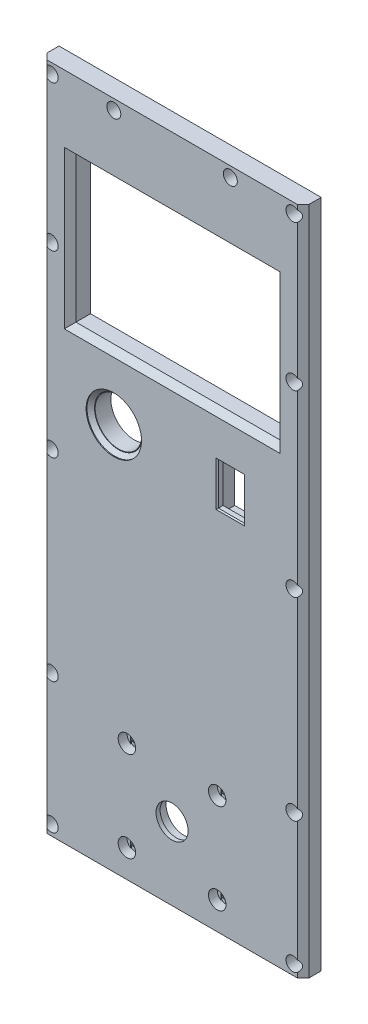
SolidWorks part; units mm, degrees
ref_plane "Front Plane" through (0, 0, 0) normal (0, 0, 1) x (1, 0, 0)
ref_plane "Top Plane" through (0, 0, 0) normal (0, 1, 0) x (1, 0, 0)
ref_plane "Right Plane" through (0, 0, 0) normal (1, 0, 0) x (0, 0, -1)
sketch "Sketch1" plane through (0, 0, 0) normal (0, 0, 1) x (1, 0, 0)
  line L1 (-45, -115) -> (45, -115)
  line L2 (-45, -115) -> (-45, 115)
  line L3 (-45, 115) -> (45, 115)
  line L4 (45, -115) -> (45, 115)
  line L5 (-45, -115) -> (45, 115) construction
  line L6 (-45, 115) -> (45, -115) construction
  line L7 (-38, -108) -> (38, -108)
  line L8 (-38, -108) -> (-38, 108)
  line L9 (-38, 108) -> (38, 108)
  line L10 (38, -108) -> (38, 108)
  line L11 (-38, -108) -> (38, 108) construction
  line L12 (-38, 108) -> (38, -108) construction
  point P0 (0, 0)
  point P6 (0, 0)
  dimension "D1" = 230
  dimension "D2" = 90
  dimension "D3" = 7
  dimension "D4" = 7
extrude "Boss-Extrude1" add sketch "Sketch1" along normal blind 7
sketch "Sketch2" plane through (0, 0, 7) normal (0, 0, 1) x (1, 0, 0)
  line L0 (38, -108) -> (38, 108) construction
  line L1 (-38, -108) -> (38, -108)
  line L2 (-38, -108) -> (-38, -58)
  line L3 (-38, -58) -> (38, -58)
  line L4 (38, -108) -> (38, -58)
  dimension "D1" = 50
extrude "Boss-Extrude2" add sketch "Sketch2" against normal up to surface (7 mm away) up to face at (0, 0, 0)
sketch "Sketch3" plane through (0, 0, 0) normal (0, 0, -1) x (-1, 0, 0)
  line L0 (0, -115) -> (0, -90) construction
  line L1 (45, -115) -> (-45, -115) construction
  circle A0 centre (0, -90) radius 5.5
  dimension "D1" = 11
  dimension "D2" = 25
extrude "Cut-Extrude1" cut sketch "Sketch3" against normal through all
sketch "Sketch4" plane through (0, 0, 0) normal (0, 0, -1) x (-1, 0, 0)
  circle A0 centre (0, -90) radius 6.05
  dimension "D1" = 12.1
extrude "Cut-Extrude2" cut sketch "Sketch4" against normal offset from surface (5.6 mm away) 1.4 up to face at (-5.5, -90, 7)
sketch "Sketch5" plane through (0, 0, 0) normal (0, 0, -1) x (-1, 0, 0)
  circle A0 centre (0, -90) radius 12
  dimension "D1" = 24
extrude "Cut-Extrude3" cut sketch "Sketch5" against normal offset from surface (3 mm away) 2.6 up to face at (-6.05, -90, 5.6)
sketch "Sketch6" plane through (0, 0, 0) normal (0, 0, -1) x (-1, 0, 0)
  line L1 (-15.5, -105.5) -> (15.5, -105.5) construction
  line L2 (-15.5, -105.5) -> (-15.5, -74.5) construction
  line L3 (-15.5, -74.5) -> (15.5, -74.5) construction
  line L4 (15.5, -105.5) -> (15.5, -74.5) construction
  line L5 (-15.5, -105.5) -> (15.5, -74.5) construction
  line L6 (-15.5, -74.5) -> (15.5, -105.5) construction
  circle A0 centre (-15.5, -74.5) radius 1.7
  circle A1 centre (15.5, -74.5) radius 1.7
  circle A2 centre (15.5, -105.5) radius 1.7
  circle A3 centre (-15.5, -105.5) radius 1.7
  point P0 (0, -90)
  dimension "D2" = 3.4
  dimension "D1" = 31
extrude "Cut-Extrude4" cut sketch "Sketch6" against normal through all
sketch "Sketch7" plane through (0, 0, 0) normal (0, 0, -1) x (-1, 0, 0)
  line L1 (-30, -112.5) -> (30, -112.5)
  line L2 (-30, -112.5) -> (-30, -67.5)
  line L3 (-30, -67.5) -> (30, -67.5)
  line L4 (30, -112.5) -> (30, -67.5)
  line L5 (-30, -112.5) -> (30, -67.5) construction
  line L6 (-30, -67.5) -> (30, -112.5) construction
  point P0 (0, -90)
  dimension "D1" = 60
  dimension "D2" = 45
extrude "Cut-Extrude5" cut sketch "Sketch7" against normal blind 1
sketch "Sketch8" plane through (0, 0, 7) normal (0, 0, 1) x (1, 0, 0)
  circle A0 centre (-15.5, -74.5) radius 3
  circle A1 centre (15.5, -74.5) radius 3
  circle A2 centre (15.5, -105.5) radius 3
  circle A3 centre (-15.5, -105.5) radius 3
  dimension "D1" = 6
extrude "Cut-Extrude6" cut sketch "Sketch8" against normal blind 3
sketch "Sketch9" plane through (0, 0, 7) normal (0, 0, 1) x (1, 0, 0)
  line L0 (-45, 115) -> (-45, -115) construction
  line L1 (-41.5, -111.5) -> (41.5, -111.5) construction
  line L2 (-41.5, -111.5) -> (-41.5, 111.5) construction
  line L3 (-41.5, 111.5) -> (41.5, 111.5) construction
  line L4 (41.5, -111.5) -> (41.5, 111.5) construction
  line L5 (-41.5, -111.5) -> (41.5, 111.5) construction
  line L6 (-41.5, 111.5) -> (41.5, -111.5) construction
  line L7 (45, 115) -> (-45, 115) construction
  circle A0 centre (-41.5, 111.5) radius 1.45
  circle A1 centre (41.5, 111.5) radius 1.45
  circle A4 centre (-41.5, -111.5) radius 1.45
  circle A5 centre (41.5, -111.5) radius 1.45
  circle A6 centre (-41.5, 61.5) radius 1.45
  circle A7 centre (41.5, 61.5) radius 1.45
  circle A8 centre (41.5, -66.5) radius 1.45
  circle A9 centre (-41.5, -66.5) radius 1.45
  circle A10 centre (-41.5, 0) radius 1.45
  circle A11 centre (41.5, 0) radius 1.45
  point P0 (0, 0)
  dimension "D3" = 2.9
  dimension "D1" = 3.5
  dimension "D2" = 3.5
  dimension "D4" = 45
  dimension "D5" = 50
extrude "Cut-Extrude7" cut sketch "Sketch9" against normal through all
sketch "Sketch10" plane through (0, 0, 7) normal (0, 0, 1) x (1, 0, 0)
  circle A0 centre (-41.5, 111.5) radius 2.4
  circle A1 centre (41.5, 61.5) radius 2.4
  circle A2 centre (-41.5, 61.5) radius 2.4
  circle A3 centre (41.5, 111.5) radius 2.4
  circle A4 centre (-41.5, -111.5) radius 2.4
  circle A5 centre (41.5, -111.5) radius 2.4
  circle A6 centre (-41.5, -66.5) radius 2.4
  circle A7 centre (41.5, -66.5) radius 2.4
  circle A8 centre (-41.5, 0) radius 2.4
  circle A9 centre (41.5, 0) radius 2.4
  dimension "D1" = 4.8
extrude "Cut-Extrude8" cut sketch "Sketch10" against normal blind 5
chamfer "Chamfer1" distance 2 angle 45 2 edges at (-45, 0, 7) (45, 0, 7)
sketch "Sketch11" plane through (0, 0, 7) normal (0, 0, 1) x (1, 0, 0)
  line L0 (38, -58) -> (38, 108) construction
  line L1 (-38, -58) -> (38, -58)
  line L2 (-38, -58) -> (-38, -36.4)
  line L3 (-38, -36.4) -> (38, -36.4)
  line L4 (38, -58) -> (38, -36.4)
  line L5 (-43, -115) -> (43, -115) construction
  dimension "D1" = 78.6
extrude "Boss-Extrude3" add sketch "Sketch11" against normal up to surface (7 mm away) up to face at (-40.05, 0, 0)
sketch "Sketch12" plane through (0, 0, 7) normal (0, 0, 1) x (1, 0, 0)
  line L0 (-41.5, 111.5) -> (41.5, 111.5) construction
  line L1 (-20, 111.5) -> (20, 111.5) construction
  circle A0 centre (-20, 111.5) radius 1.45
  circle A1 centre (20, 111.5) radius 1.45
  circle A2 centre (-41.5, 111.5) radius 1.45 construction
  point P7 (0, 111.5)
  dimension "D1" = 40
extrude "Cut-Extrude9" cut sketch "Sketch12" against normal through all
sketch "Sketch13" plane through (0, 0, 7) normal (0, 0, 1) x (1, 0, 0)
  circle A0 centre (-20, 111.5) radius 2.4
  circle A1 centre (20, 111.5) radius 2.4
  circle A2 centre (-41.5, 111.5) radius 2.4 construction
extrude "Cut-Extrude10" cut sketch "Sketch13" against normal up to surface (5 mm away) up to face at (-39.1, 111.5, 2)
chamfer "Chamfer2" distance 0.8 angle 45 12 edges at (0, -115, 0) (-45, 0, 0) (0, 115, 0) (45, 0, 0) (38, 35.8, 7) (0, 108, 7) (-38, 35.8, 7) (0, -36.4, 7) (-38, 35.8, 0) (0, 108, 0) (38, 35.8, 0) (0, -36.4, 0)
sketch "Sketch14" plane through (0, 0, 2) normal (0, 0, 1) x (1, 0, 0)
  line L2 (-42.95, -68.4125) -> (-42.95, -64.5875)
  line L4 (-40.05, -68.4125) -> (-40.05, -64.5875)
  line L5 (-42.95, -68.4125) -> (-40.05, -64.5875) construction
  line L6 (-42.95, -64.5875) -> (-40.05, -68.4125) construction
  line L14 (-42.95, -113.4125) -> (-42.95, -109.5875)
  line L16 (-40.05, -113.4125) -> (-40.05, -109.5875)
  line L17 (-42.95, -113.4125) -> (-40.05, -109.5875) construction
  line L18 (-42.95, -109.5875) -> (-40.05, -113.4125) construction
  line L26 (-42.95, 59.5875) -> (-42.95, 63.4125)
  line L28 (-40.05, 59.5875) -> (-40.05, 63.4125)
  line L29 (-42.95, 59.5875) -> (-40.05, 63.4125) construction
  line L30 (-42.95, 63.4125) -> (-40.05, 59.5875) construction
  line L32 (-21.45, 109.5875) -> (-21.45, 113.4125)
  line L34 (-18.55, 109.5875) -> (-18.55, 113.4125)
  line L35 (-21.45, 109.5875) -> (-18.55, 113.4125) construction
  line L36 (-21.45, 113.4125) -> (-18.55, 109.5875) construction
  line L38 (-42.95, 109.5875) -> (-42.95, 113.4125)
  line L40 (-40.05, 109.5875) -> (-40.05, 113.4125)
  line L41 (-42.95, 109.5875) -> (-40.05, 113.4125) construction
  line L42 (-42.95, 113.4125) -> (-40.05, 109.5875) construction
  arc A0 (-43, -68.3735) -> (-43, -64.6265) centre (-41.5, -66.5) ccw construction
  circle A2 centre (-41.5, -111.5) radius 2.4 construction
  circle A4 centre (-41.5, 61.5) radius 2.4 construction
  circle A5 centre (-20, 111.5) radius 2.4 construction
  circle A6 centre (-41.5, 111.5) radius 2.4 construction
  circle A7 centre (-41.5, 111.5) radius 1.45 construction
  circle A8 centre (-20, 111.5) radius 1.45 construction
  circle A9 centre (-41.5, 61.5) radius 1.45 construction
  circle A10 centre (-41.5, -66.5) radius 1.45 construction
  circle A12 centre (-41.5, -111.5) radius 1.45 construction
  arc A16 (-21.45, 109.5875) -> (-18.55, 109.5875) centre (-20, 111.5) ccw
  arc A17 (-40.05, 113.4125) -> (-42.95, 113.4125) centre (-41.5, 111.5) ccw
  arc A18 (-40.05, 63.4125) -> (-42.95, 63.4125) centre (-41.5, 61.5) ccw
  arc A20 (-42.95, -68.4125) -> (-40.05, -68.4125) centre (-41.5, -66.5) ccw
  arc A22 (-40.05, -109.5875) -> (-42.95, -109.5875) centre (-41.5, -111.5) ccw
  arc A23 (-42.95, 109.5875) -> (-40.05, 109.5875) centre (-41.5, 111.5) ccw
  arc A24 (-18.55, 113.4125) -> (-21.45, 113.4125) centre (-20, 111.5) ccw
  arc A25 (-42.95, 59.5875) -> (-40.05, 59.5875) centre (-41.5, 61.5) ccw
  arc A26 (-40.05, -64.5875) -> (-42.95, -64.5875) centre (-41.5, -66.5) ccw
  arc A29 (-42.95, -113.4125) -> (-40.05, -113.4125) centre (-41.5, -111.5) ccw
  point P0 (-41.5, -66.5)
  point P17 (-41.5, -111.5)
  point P33 (-41.5, 61.5)
  point P41 (-20, 111.5)
  point P49 (-41.5, 111.5)
extrude "Cut-Extrude11" cut sketch "Sketch14" against normal blind 0.2
sketch "Sketch15" plane through (0, 0, 1.8) normal (0, 0, 1) x (1, 0, 0)
  line L0 (-40.05, -111.5) -> (-40.05, -109.5875) construction
  line L1 (-42.95, -112.95) -> (-40.05, -112.95)
  line L2 (-42.95, -112.95) -> (-42.95, -110.05)
  line L3 (-42.95, -110.05) -> (-40.05, -110.05)
  line L4 (-40.05, -112.95) -> (-40.05, -110.05)
  line L5 (-42.95, -112.95) -> (-40.05, -110.05) construction
  line L6 (-42.95, -110.05) -> (-40.05, -112.95) construction
  line L7 (-40.05, 61.5) -> (-40.05, 63.4125) construction
  line L8 (-42.95, -67.95) -> (-40.05, -67.95)
  line L9 (-42.95, -67.95) -> (-42.95, -65.05)
  line L10 (-42.95, -65.05) -> (-40.05, -65.05)
  line L11 (-40.05, -67.95) -> (-40.05, -65.05)
  line L12 (-42.95, -67.95) -> (-40.05, -65.05) construction
  line L13 (-42.95, -65.05) -> (-40.05, -67.95) construction
  line L14 (-42.95, 60.05) -> (-40.05, 60.05)
  line L15 (-42.95, 60.05) -> (-42.95, 62.95)
  line L16 (-42.95, 62.95) -> (-40.05, 62.95)
  line L17 (-40.05, 60.05) -> (-40.05, 62.95)
  line L18 (-42.95, 60.05) -> (-40.05, 62.95) construction
  line L19 (-42.95, 62.95) -> (-40.05, 60.05) construction
  line L20 (-40.05, 109.5875) -> (-40.05, 113.4125) construction
  line L21 (-42.95, 110.05) -> (-40.05, 110.05)
  line L22 (-42.95, 110.05) -> (-42.95, 112.95)
  line L23 (-42.95, 112.95) -> (-40.05, 112.95)
  line L24 (-40.05, 110.05) -> (-40.05, 112.95)
  line L25 (-42.95, 110.05) -> (-40.05, 112.95) construction
  line L26 (-42.95, 112.95) -> (-40.05, 110.05) construction
  line L27 (-18.55, 109.5875) -> (-18.55, 113.4125) construction
  line L28 (-21.45, 110.05) -> (-18.55, 110.05)
  line L29 (-21.45, 110.05) -> (-21.45, 112.95)
  line L30 (-21.45, 112.95) -> (-18.55, 112.95)
  line L31 (-18.55, 110.05) -> (-18.55, 112.95)
  line L32 (-21.45, 110.05) -> (-18.55, 112.95) construction
  line L33 (-21.45, 112.95) -> (-18.55, 110.05) construction
  arc A0 (-40.05, -66.5) -> (-42.95, -66.5) centre (-41.5, -66.5) ccw construction
  arc A1 (-40.05, 61.5) -> (-42.95, 61.5) centre (-41.5, 61.5) ccw construction
  arc A2 (-18.55, 111.5) -> (-21.45, 111.5) centre (-20, 111.5) ccw construction
  arc A3 (-40.05, 111.5) -> (-42.95, 111.5) centre (-41.5, 111.5) ccw construction
  point P0 (-41.5, -111.5)
  point P8 (-41.5, -66.5)
  point P17 (-41.5, 61.5)
  point P28 (-41.5, 111.5)
  point P36 (-20, 111.5)
extrude "Cut-Extrude12" cut sketch "Sketch15" against normal blind 0.2
sketch "Sketch16" plane through (0, 0, 4) normal (0, 0, 1) x (1, 0, 0)
  line L2 (-17.2, -76.9718) -> (-17.2, -72.0282)
  line L4 (-13.8, -76.9718) -> (-13.8, -72.0282)
  line L5 (-17.2, -76.9718) -> (-13.8, -72.0282) construction
  line L6 (-17.2, -72.0282) -> (-13.8, -76.9718) construction
  line L8 (-17.2, -107.9718) -> (-17.2, -103.0282)
  line L10 (-13.8, -107.9718) -> (-13.8, -103.0282)
  line L11 (-17.2, -107.9718) -> (-13.8, -103.0282) construction
  line L12 (-17.2, -103.0282) -> (-13.8, -107.9718) construction
  circle A0 centre (-15.5, -74.5) radius 3 construction
  circle A1 centre (-15.5, -105.5) radius 3 construction
  circle A2 centre (-15.5, -105.5) radius 1.7 construction
  circle A3 centre (-15.5, -74.5) radius 1.7 construction
  circle A4 centre (-15.5, -105.5) radius 3 construction
  circle A5 centre (-15.5, -74.5) radius 3 construction
  arc A6 (-13.8, -103.0282) -> (-17.2, -103.0282) centre (-15.5, -105.5) ccw
  arc A7 (-17.2, -76.9718) -> (-13.8, -76.9718) centre (-15.5, -74.5) ccw
  arc A8 (-13.8, -72.0282) -> (-17.2, -72.0282) centre (-15.5, -74.5) ccw
  arc A9 (-17.2, -107.9718) -> (-13.8, -107.9718) centre (-15.5, -105.5) ccw
  point P0 (-15.5, -74.5)
  point P8 (-15.5, -105.5)
extrude "Cut-Extrude13" cut sketch "Sketch16" against normal blind 0.2
sketch "Sketch17" plane through (0, 0, 3.8) normal (0, 0, 1) x (1, 0, 0)
  line L0 (-13.8, -76.9718) -> (-13.8, -72.0282) construction
  line L1 (-17.2, -76.2) -> (-13.8, -76.2)
  line L2 (-17.2, -76.2) -> (-17.2, -72.8)
  line L3 (-17.2, -72.8) -> (-13.8, -72.8)
  line L4 (-13.8, -76.2) -> (-13.8, -72.8)
  line L5 (-17.2, -76.2) -> (-13.8, -72.8) construction
  line L6 (-17.2, -72.8) -> (-13.8, -76.2) construction
  line L7 (-13.8, -107.9718) -> (-13.8, -103.0282) construction
  line L8 (-17.2, -107.2) -> (-13.8, -107.2)
  line L9 (-17.2, -107.2) -> (-17.2, -103.8)
  line L10 (-17.2, -103.8) -> (-13.8, -103.8)
  line L11 (-13.8, -107.2) -> (-13.8, -103.8)
  line L12 (-17.2, -107.2) -> (-13.8, -103.8) construction
  line L13 (-17.2, -103.8) -> (-13.8, -107.2) construction
  arc A0 (-13.8, -105.5) -> (-17.2, -105.5) centre (-15.5, -105.5) ccw construction
  arc A1 (-13.8, -74.5) -> (-17.2, -74.5) centre (-15.5, -74.5) ccw construction
  point P0 (-15.5, -74.5)
  point P8 (-15.5, -105.5)
extrude "Cut-Extrude14" cut sketch "Sketch17" against normal blind 0.2
mirror "Mirror1" about plane through (0, 0, 0) normal (1, 0, 0) of "Cut-Extrude12", "Cut-Extrude13", "Cut-Extrude14", "Cut-Extrude11"
sketch "Sketch18" plane through (0, 0, 7) normal (0, 0, 1) x (1, 0, 0)
  line L0 (38.8, 108.8) -> (38.8, -37.2) construction
  line L1 (-38.8, 108.8) -> (38.8, 108.8)
  line L2 (-38.8, 108.8) -> (-38.8, 70.8)
  line L3 (-38.8, 70.8) -> (38.8, 70.8)
  line L4 (38.8, 108.8) -> (38.8, 70.8)
  dimension "D1" = 38
extrude "Boss-Extrude4" add sketch "Sketch18" against normal up to surface (7 mm away) up to face at (0, 35.8, 0)
chamfer "Chamfer3" distance 0.8 angle 45 1 edges at (0, 70.8, 7)
sketch "Sketch19" plane through (0, 0, 7) normal (0, 0, 1) x (1, 0, 0)
  line L1 (-38.8, 71.6) -> (38.8, 71.6)
  line L2 (-38.8, 71.6) -> (-38.8, -37.2)
  line L3 (-38.8, -37.2) -> (38.8, -37.2)
  line L4 (38.8, 71.6) -> (38.8, -37.2)
extrude "Boss-Extrude5" add sketch "Sketch19" against normal up to surface (7 mm away) up to face at (0, 16.8, 0)
sketch "Sketch20" plane through (0, 0, 2) normal (0, 0, 1) x (1, 0, 0)
  line L2 (-42.95, -1.9125) -> (-42.95, 1.9125)
  line L4 (-40.05, -1.9125) -> (-40.05, 1.9125)
  line L5 (-42.95, -1.9125) -> (-40.05, 1.9125) construction
  line L6 (-42.95, 1.9125) -> (-40.05, -1.9125) construction
  arc A0 (-43, -1.8735) -> (-43, 1.8735) centre (-41.5, 0) ccw construction
  circle A1 centre (-41.5, 0) radius 1.45 construction
  arc A2 (-42.95, -1.9125) -> (-40.05, -1.9125) centre (-41.5, 0) ccw
  arc A3 (-40.05, 1.9125) -> (-42.95, 1.9125) centre (-41.5, 0) ccw
  point P0 (-41.5, 0)
extrude "Cut-Extrude15" cut sketch "Sketch20" against normal blind 0.2
sketch "Sketch21" plane through (0, 0, 1.8) normal (0, 0, 1) x (1, 0, 0)
  line L0 (-40.05, -1.9125) -> (-40.05, 1.9125) construction
  line L1 (-42.95, -1.45) -> (-40.05, -1.45)
  line L2 (-42.95, -1.45) -> (-42.95, 1.45)
  line L3 (-42.95, 1.45) -> (-40.05, 1.45)
  line L4 (-40.05, -1.45) -> (-40.05, 1.45)
  line L5 (-42.95, -1.45) -> (-40.05, 1.45) construction
  line L6 (-42.95, 1.45) -> (-40.05, -1.45) construction
  arc A0 (-40.05, 0) -> (-42.95, 0) centre (-41.5, 0) ccw construction
  point P0 (-41.5, 0)
extrude "Cut-Extrude16" cut sketch "Sketch21" against normal blind 0.2
mirror "Mirror2" about plane through (0, 0, 0) normal (1, 0, 0) of "Cut-Extrude16", "Cut-Extrude15"
sketch "Sketch22" plane through (0, 0, 7) normal (0, 0, 1) x (1, 0, 0)
  line L0 (43, 115) -> (-43, 115) construction
  line L1 (-35, 40) -> (35, 40)
  line L2 (-35, 40) -> (-35, 90)
  line L3 (-35, 90) -> (35, 90)
  line L4 (35, 40) -> (35, 90)
  line L5 (-35, 40) -> (35, 90) construction
  line L6 (-35, 90) -> (35, 40) construction
  point P0 (0, 65)
  point P5 (0, 0)
  dimension "D1" = 25
  dimension "D2" = 70
  dimension "D3" = 50
extrude "Cut-Extrude17" cut sketch "Sketch22" against normal through all
chamfer "Chamfer4" distance 2 angle 45 4 edges at (-35, 65, 7) (0, 40, 7) (35, 65, 7) (0, 90, 7)
sketch "Sketch23" plane through (0, 0, 7) normal (0, 0, 1) x (1, 0, 0)
  line L0 (-20, 18) -> (20, 18) construction
  line L1 (15.5, 10.75) -> (24.5, 10.75)
  line L2 (15.5, 10.75) -> (15.5, 25.25)
  line L3 (15.5, 25.25) -> (24.5, 25.25)
  line L4 (24.5, 10.75) -> (24.5, 25.25)
  line L5 (15.5, 10.75) -> (24.5, 25.25) construction
  line L6 (15.5, 25.25) -> (24.5, 10.75) construction
  circle A0 centre (-20, 18) radius 8
  point P0 (20, 18)
  point P7 (0, 18)
  dimension "D3" = 16
  dimension "D1" = 9
  dimension "D2" = 14.5
  dimension "D4" = 18
  dimension "D5" = 40
extrude "Cut-Extrude18" cut sketch "Sketch23" against normal through all
sketch "Sketch24" plane through (0, 0, 0) normal (0, 0, -1) x (-1, 0, 0)
  line L0 (-15.5, 25.25) -> (-24.5, 10.75) construction
  line L1 (-24.5, 25.25) -> (-15.5, 25.25) construction
  line L2 (-25.5, 7.75) -> (-14.5, 7.75)
  line L3 (-25.5, 7.75) -> (-25.5, 28.25)
  line L4 (-25.5, 28.25) -> (-14.5, 28.25)
  line L5 (-14.5, 7.75) -> (-14.5, 28.25)
  line L6 (-25.5, 7.75) -> (-14.5, 28.25) construction
  line L7 (-25.5, 28.25) -> (-14.5, 7.75) construction
  line L8 (-15.5, 25.25) -> (-15.5, 10.75) construction
  point P4 (-20, 18)
  dimension "D1" = 3
  dimension "D2" = 1
extrude "Cut-Extrude19" cut sketch "Sketch24" against normal offset from surface (5 mm away) 2 up to face at (20, 18, 7)
sketch "Sketch25" plane through (0, 0, 7) normal (0, 0, 1) x (1, 0, 0)
  circle A0 centre (-20, 18) radius 9.5
  dimension "D1" = 19
extrude "Cut-Extrude20" cut sketch "Sketch25" against normal blind 1.6
chamfer "Chamfer5" distance 1.3 angle 45 1 edges at (-10.5, 18, 5.4)
chamfer "Chamfer6" distance 0.4 angle 45 4 edges at (15.5, 18, 7) (20, 10.75, 7) (24.5, 18, 7) (20, 25.25, 7)
sketch "Sketch26" plane through (0, 0, 0) normal (0, 0, -1) x (-1, 0, 0)
  circle A0 centre (0, -5) radius 1.7
  circle A1 centre (10, -5) radius 1.7
  circle A2 centre (20, -5) radius 1.7
  circle A3 centre (30, -5) radius 1.7
  circle A4 centre (10, -15) radius 1.7
  circle A5 centre (20, -15) radius 1.7
  circle A6 centre (30, -15) radius 1.7
  circle A7 centre (10, -25) radius 1.7
  circle A8 centre (20, -25) radius 1.7
  circle A9 centre (30, -25) radius 1.7
  circle A10 centre (10, -35) radius 1.7
  circle A11 centre (20, -35) radius 1.7
  circle A12 centre (30, -35) radius 1.7
  circle A13 centre (10, -45) radius 1.7
  circle A14 centre (20, -45) radius 1.7
  circle A15 centre (30, -45) radius 1.7
  circle A16 centre (0, -15) radius 1.7
  circle A17 centre (0, -25) radius 1.7
  circle A18 centre (0, -35) radius 1.7
  circle A19 centre (0, -45) radius 1.7
  dimension "D1" = 3.4
  dimension "D2" = 5
  dimension "D3" = 4
  dimension "D4" = 5
extrude "Cut-Extrude21" cut sketch "Sketch26" against normal blind 4
mirror "Mirror3" about plane through (0, 0, 0) normal (1, 0, 0) of "Cut-Extrude21"
